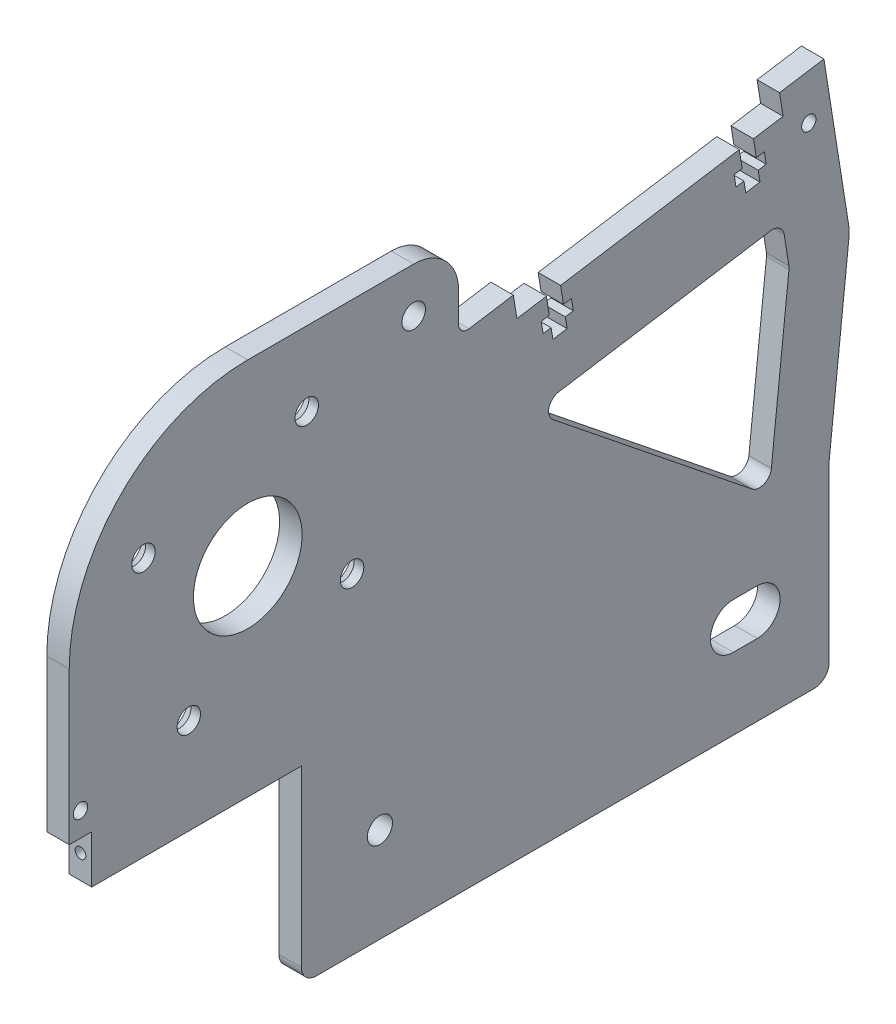
SolidWorks part; units mm, degrees
ref_plane "Front Plane" through (0, 0, 0) normal (0, 0, 1) x (1, 0, 0)
ref_plane "Top Plane" through (0, 0, 0) normal (0, 1, 0) x (1, 0, 0)
ref_plane "Right Plane" through (0, 0, 0) normal (1, 0, 0) x (0, 0, -1)
sketch "Sketch1" plane through (0, 0, 0) normal (1, 0, 0) x (0, 0, -1)
  line L0 (-28.1703, 0) -> (77.3828, 0)
  line L1 (80.5578, 3.175) -> (80.5578, 40.132)
  line L2 (-80.5578, 82.55) -> (-80.5578, 50.292)
  line L3 (4.1952, 102.6435) -> (13.6029, 104.1335)
  line L4 (-75.7953, 50.292) -> (-75.7953, 40.132)
  line L5 (-80.5578, 50.292) -> (-75.7953, 50.292)
  line L6 (65.3178, 20.066) -> (60.2378, 20.066) construction
  line L7 (-75.7953, 40.132) -> (-31.3453, 40.132)
  line L8 (1.9922, 110.875) -> (1.9922, 104.525)
  line L9 (-42.7078, 120.4) -> (-7.5328, 120.4)
  line L10 (-31.3453, 40.132) -> (-31.3453, 3.175)
  line L11 (-37.7935, 96.5728) -> (77.9184, 56.022) construction
  line L12 (-52.4128, 71.2982) -> (40.4331, -8.7847) construction
  line L13 (65.3178, 15.2273) -> (60.2378, 15.2273)
  line L14 (65.3178, 24.9047) -> (60.2378, 24.9047)
  line L15 (4.1952, 102.6435) -> (101.0919, 102.6435) construction
  line L16 (13.6029, 104.1335) -> (14.348, 99.4297)
  line L17 (14.348, 99.4297) -> (20.6198, 100.423)
  line L18 (70.7944, 108.3699) -> (70.0493, 113.0738)
  line L19 (70.0493, 113.0738) -> (79.4571, 114.5638)
  line L20 (79.4571, 114.5638) -> (84.7184, 81.3449)
  line L21 (84.7717, 79.1961) -> (80.5578, 40.132)
  line L22 (20.6198, 100.423) -> (21.2208, 96.6286)
  line L23 (21.2208, 96.6286) -> (19.5274, 96.3604)
  line L24 (19.5274, 96.3604) -> (19.9198, 93.883)
  line L25 (19.9198, 93.883) -> (21.6131, 94.1512)
  line L26 (26.317, 94.8962) -> (25.9246, 97.3736)
  line L27 (25.9246, 97.3736) -> (24.2312, 97.1054)
  line L28 (24.2312, 97.1054) -> (23.6303, 100.8998)
  line L29 (23.6303, 100.8998) -> (61.5121, 106.8997)
  line L30 (64.5225, 107.3765) -> (70.7944, 108.3699)
  line L31 (71.0359, 86.549) -> (72.0272, 80.29)
  line L38 (21.6131, 94.1512) -> (21.9857, 91.7993)
  line L39 (21.9857, 91.7993) -> (24.9961, 92.2761)
  line L40 (24.9961, 92.2761) -> (24.6236, 94.628)
  line L41 (24.6236, 94.628) -> (26.317, 94.8962)
  line L46 (61.5121, 106.8997) -> (62.113, 103.1053)
  line L47 (68.1298, 88.6604) -> (23.2189, 81.5472)
  line L48 (22.0267, 77.0573) -> (64.1879, 43.2308)
  line L49 (68.3027, 44.9396) -> (72.0438, 79.6202)
  line L50 (62.113, 103.1053) -> (60.4196, 102.8371)
  line L51 (60.4196, 102.8371) -> (60.812, 100.3597)
  line L52 (60.812, 100.3597) -> (62.5054, 100.6279)
  line L53 (67.2093, 101.3729) -> (66.8169, 103.8503)
  line L54 (66.8169, 103.8503) -> (65.1235, 103.5821)
  line L55 (65.1235, 103.5821) -> (64.5225, 107.3765)
  line L56 (62.5054, 100.6279) -> (62.8779, 98.276)
  line L57 (62.8779, 98.276) -> (65.8884, 98.7528)
  line L58 (65.8884, 98.7528) -> (65.5159, 101.1047)
  line L59 (65.5159, 101.1047) -> (67.2093, 101.3729)
  arc A0 (65.3178, 15.2273) -> (65.3178, 24.9047) centre (65.3178, 20.066) ccw
  circle A1 centre (-42.7078, 82.55) radius 31.5 construction
  circle A2 centre (65.3178, 20.066) radius 78.105 construction
  circle A3 centre (65.3178, 20.066) radius 38.1 construction
  circle A4 centre (-42.7078, 82.55) radius 14.859 construction
  arc A5 (-42.7078, 120.4) -> (-80.5578, 82.55) centre (-42.7078, 82.55) ccw
  arc A6 (-28.1703, 0) -> (-31.3453, 3.175) centre (-28.1703, 3.175) cw
  arc A7 (77.3828, 0) -> (80.5578, 3.175) centre (77.3828, 3.175) ccw
  circle A9 centre (-7.5328, 110.875) radius 6.35 construction
  circle A10 centre (-55.209, 60.4394) radius 2.4892
  circle A11 centre (-14.6922, 20.066) radius 2.667
  circle A12 centre (-20.5972, 70.0488) radius 2.4892
  circle A13 centre (-64.8184, 95.0512) radius 2.4892
  circle A14 centre (-30.2065, 104.6606) radius 2.4892
  circle A15 centre (-78.1765, 55.372) radius 1.524
  circle A16 centre (-42.7078, 82.55) radius 11.5228
  arc A17 (60.2378, 24.9047) -> (60.2378, 15.2273) centre (60.2378, 20.066) ccw
  arc A18 (-7.5328, 120.4) -> (1.9922, 110.875) centre (-7.5328, 110.875) cw
  circle A19 centre (-7.5328, 110.875) radius 2.4892
  arc A20 (4.1952, 102.6435) -> (1.9922, 104.525) centre (3.8972, 104.525) cw
  arc A21 (84.7184, 81.3449) -> (84.7717, 79.1961) centre (76.6695, 80.0701) cw
  circle A22 centre (76.2432, 104.411) radius 1.524
  arc A23 (72.0438, 79.6202) -> (72.0272, 80.29) centre (69.5185, 79.8927) ccw
  arc A24 (64.1879, 43.2308) -> (68.3027, 44.9396) centre (65.7774, 45.212) ccw
  arc A25 (23.2189, 81.5472) -> (22.0267, 77.0573) centre (23.6162, 79.0385) ccw
  arc A26 (68.1298, 88.6604) -> (71.0359, 86.549) centre (68.5271, 86.1517) cw
  point P39 (62.7778, 20.066)
  dimension "D4" = 9.6774
  dimension "D7" = 29.718
  dimension "D8" = 63
  dimension "D9" = 6.35
  dimension "D12" = 3.175
  dimension "D13" = 4.7625
  dimension "D14" = 76.2
  dimension "D15" = 156.21
  dimension "D18" = 5.334
  dimension "D19" = 9.525
  dimension "D20" = 9.525
  dimension "D23" = 3.048
  dimension "D27" = 73.025
  dimension "D28" = 12.7
  dimension "D29" = 4.9784
  dimension "D31" = 1.905
  dimension "D33" = 3.048
  dimension "D42" = 2.54
  dimension "D43" = 2.54
  dimension "D44" = 86.36
  dimension "D48" = 3.048
  dimension "D49" = 9.525
  dimension "D2" = 40.132
  dimension "D3" = 20.066
  dimension "D5" = 15.24
  dimension "D6" = 44.45
  dimension "D10" = 161.1156
  dimension "D11" = 95.25
  dimension "D17" = 9
  dimension "D21" = 4.7625
  dimension "D22" = 10.16
  dimension "D24" = 5.08
  dimension "D25" = 2.3813
  dimension "D26" = 5.08
  dimension "D16" = 76.2
  dimension "D30" = 9.525
  dimension "D34" = 19.05
  dimension "D35" = 8.7312
  dimension "D36" = 2.5083
  dimension "D37" = 6.477
  dimension "D38" = 6.35
  dimension "D40" = 12.7
  dimension "D45" = 6.35
  dimension "D46" = 6.35
  dimension "D47" = 4.7625
  dimension "D50" = 5.08
  dimension "D39" = 2
extrude "Boss-Extrude1" add sketch "Sketch1" along normal blind 4.7625
sketch "Sketch2" plane through (0, 0, 75.7953) normal (0, 0, 1) x (1, 0, 0)
  line L0 (4.7625, 50.292) -> (4.7625, 40.132) construction
  line L1 (4.7625, 40.132) -> (0, 40.132) construction
  circle A0 centre (2.3813, 45.212) radius 1.1303
  point P4 (4.7625, 45.212)
  point P7 (2.3813, 40.132)
  dimension "D1" = 2.2606
extrude "Cut-Extrude1" cut sketch "Sketch2" against normal blind 6.35
chamfer "Chamfer1" distance 2.7305 angle 41 4 edges at (0, 95.0512, 62.3292) (0, 60.4394, 52.7198) (0, 70.0488, 18.108) (0, 104.6606, 27.7173) first distance on face at (4.7625, 95.0512, 62.3292) first distance on face at (4.7625, 60.4394, 52.7198) first distance on face at (4.7625, 70.0488, 18.108) first distance on face at (4.7625, 104.6606, 27.7173)
